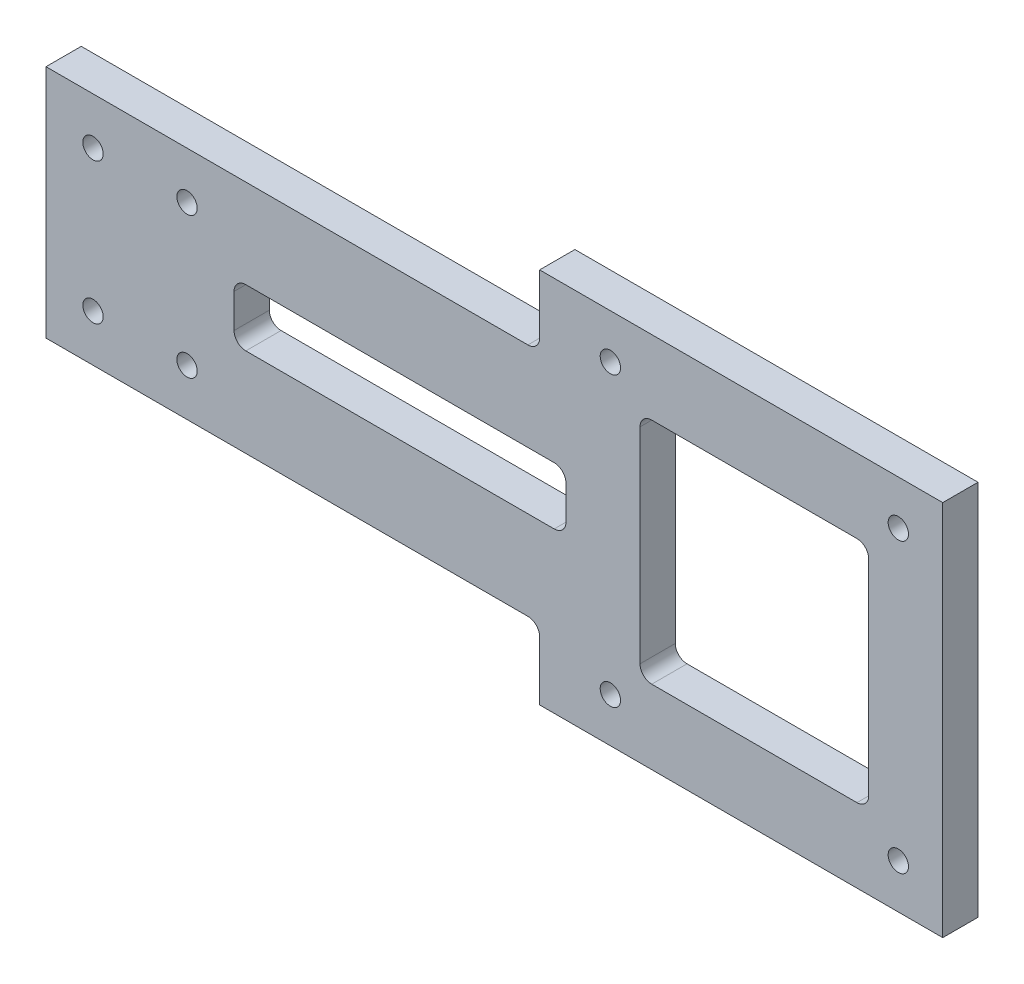
SolidWorks part; units mm, degrees
material "6061-T6 (SS)"
ref_plane "Front" through (0, 0, 0) normal (0, 0, 1) x (1, 0, 0)
ref_plane "Top" through (0, 0, 0) normal (0, 1, 0) x (1, 0, 0)
ref_plane "Right" through (0, 0, 0) normal (1, 0, 0) x (0, 0, -1)
sketch "Sketch1" plane through (0, 0, 0) normal (0, 0, 1) x (1, 0, 0)
  line L0 (101.6, 31.75) -> (101.6, 50.8909)
  line L1 (101.6, 31.75) -> (-31.75, 31.75)
  line L3 (101.6, -31.75) -> (-31.75, -31.75)
  line L4 (-31.75, 31.75) -> (-31.75, -31.75)
  line L5 (-31.75, -31.75) -> (0, 0) construction
  line L6 (0, 0) -> (-31.75, 31.75) construction
  line L7 (101.6, 50.8909) -> (210.4909, 50.8909)
  line L8 (210.4909, 50.8909) -> (210.4909, 30.8909)
  line L9 (210.4909, 30.8909) -> (128.7091, 30.8909)
  line L10 (128.7091, 30.8909) -> (128.7091, -30.8909)
  line L11 (128.7091, -30.8909) -> (210.4909, -30.8909)
  line L12 (210.4909, -30.8909) -> (210.4909, -50.8909)
  line L13 (210.4909, -50.8909) -> (101.6, -50.8909)
  line L14 (101.6, -50.8909) -> (101.6, -31.75)
  line L15 (198.4909, -30.8909) -> (198.4909, -38.8909) construction
  line L16 (198.4909, -38.8909) -> (198.4909, -50.8909) construction
  line L17 (0, 0) -> (159.6, 0) construction
  line L18 (198.4909, -38.8909) -> (120.7091, 38.8909) construction
  line L19 (198.4909, 38.8909) -> (120.7091, -38.8909) construction
  line L20 (128.7091, 30.8909) -> (159.6, 0) construction
  line L21 (159.6, 0) -> (128.7091, -30.8909) construction
  line L22 (198.4909, 38.8909) -> (198.4909, 50.8909) construction
  line L23 (198.4909, 38.8909) -> (210.4909, 38.8909) construction
  line L24 (198.4909, 38.8909) -> (198.4909, 30.8909) construction
  line L25 (120.7091, 38.8909) -> (101.6, 38.8909) construction
  line L26 (0, 0) -> (128.7091, 0) construction
  line L27 (0, 0) -> (101.6, -31.75) construction
  line L28 (0, 0) -> (101.6, 31.75) construction
  line L29 (198.4909, -38.8909) -> (210.4909, -38.8909) construction
  line L30 (159.6, 0) -> (159.6, 30.8909) construction
  line L31 (159.6, 0) -> (128.7091, 0) construction
  circle A0 centre (159.6, 0) radius 55 construction
  point P0 (0, 0)
  point P17 (198.4909, 38.8909)
  point P18 (198.4909, -38.8909)
  point P19 (120.7091, 38.8909)
  point P20 (120.7091, -38.8909)
  dimension "D2" = 110
  dimension "D1" = 63.5
  dimension "D3" = 90
  dimension "D5" = 8
  dimension "D6" = 12
  dimension "D7" = 133.35
  dimension "D9" = 58
  dimension "D10" = 0
extrude "Boss-Extrude1" add sketch "Sketch1" along normal blind 9.525
hole_wizard "M5 Clearance Hole1" positions "Sketch3" profile "Sketch4" hole size "M5" standard "ANSI Metric"
sketch "Sketch3" plane through (0, 0, 9.525) normal (0, 0, 1) x (1, 0, 0)
  line L0 (0, 0) -> (159.6, 0) construction
  line L2 (198.4909, -38.8909) -> (120.7091, 38.8909) construction
  line L4 (198.4909, 38.8909) -> (120.7091, -38.8909) construction
  line L6 (128.7091, 30.8909) -> (159.6, 0) construction
  line L7 (159.6, 0) -> (128.7091, -30.8909) construction
  line L8 (101.6, 31.75) -> (-31.75, 31.75) construction
  line L12 (101.6, -31.75) -> (101.6, -50.8909) construction
  circle A0 centre (159.6, 0) radius 55 construction
  point P0 (198.4909, 38.8909)
  point P2 (198.4909, -38.8909)
  point P4 (120.7091, 38.8909)
  point P6 (120.7091, -38.8909)
  dimension "D1" = 110
  dimension "D2" = 135
  dimension "D3" = 90
  dimension "D4" = 58
sketch "Sketch4" plane through (198.4909, 38.8909, 9.525) normal (1, 0, 0) x (0, -1, 0)
  line L0 (0, 0) -> (0, 20.4024)
  line L1 (0, 20.4024) -> (2.75, 18.75)
  line L2 (2.75, 18.75) -> (2.75, 0)
  line L5 (2.75, 0) -> (0, 0)
  line L10 (0, 20.4024) -> (-2.75, 18.75) construction
  line L11 (0, -6.35) -> (0, 107.95) construction
  dimension "Hole Dia." = 5.5
  dimension "Hole Depth" = 18.75
  dimension "Drill Angle" = 118
fillet "Fillet1" radius 3.175 4 edges at (128.7091, 30.8909, 4.7625) (128.7091, -30.8909, 4.7625) (101.6, -31.75, 4.7625) (101.6, 31.75, 4.7625)
hole_wizard "M5 Clearance Hole2" positions "Sketch5" profile "Sketch6" hole size "M5" standard "ANSI Metric"
sketch "Sketch5" plane through (0, 0, 9.525) normal (0, 0, 1) x (1, 0, 0)
  line L0 (-19.05, 19.05) -> (6.35, 19.05) construction
  line L1 (6.35, 19.05) -> (6.35, -19.05) construction
  line L2 (6.35, -19.05) -> (-19.05, -19.05) construction
  line L3 (-19.05, -19.05) -> (-19.05, 19.05) construction
  line L5 (98.425, 31.75) -> (-31.75, 31.75) construction
  line L9 (-31.75, -31.75) -> (-19.05, -19.05) construction
  line L11 (-19.05, 19.05) -> (-31.75, 31.75) construction
  point P0 (-19.05, 19.05)
  point P2 (6.35, 19.05)
  point P4 (6.35, -19.05)
  point P6 (-19.05, -19.05)
  dimension "D1" = 12.7
  dimension "D2" = 25.4
sketch "Sketch6" plane through (-19.05, 19.05, 9.525) normal (1, 0, 0) x (0, -1, 0)
  line L0 (0, 0) -> (0, 20.4024)
  line L1 (0, 20.4024) -> (2.75, 18.75)
  line L2 (2.75, 18.75) -> (2.75, 0)
  line L5 (2.75, 0) -> (0, 0)
  line L10 (0, 20.4024) -> (-2.75, 18.75) construction
  line L11 (0, -6.35) -> (0, 107.95) construction
  dimension "Hole Dia." = 5.5
  dimension "Hole Depth" = 18.75
  dimension "Drill Angle" = 118
sketch "Sketch7" plane through (0, 0, 9.525) normal (0, 0, 1) x (1, 0, 0)
  line L0 (6.35, 19.05) -> (6.35, 31.75) construction
  line L1 (108.7091, -7.75) -> (19.05, -7.75)
  line L2 (108.7091, -7.75) -> (108.7091, 7.75)
  line L3 (108.7091, 7.75) -> (19.05, 7.75)
  line L4 (19.05, -7.75) -> (19.05, 7.75)
  line L5 (108.7091, -7.75) -> (19.05, 7.75) construction
  line L6 (108.7091, 7.75) -> (19.05, -7.75) construction
  line L7 (128.7091, -27.7159) -> (128.7091, 27.7159) construction
  line L8 (98.425, 31.75) -> (-31.75, 31.75) construction
  line L9 (0, 0) -> (63.8796, 0) construction
  line L10 (6.35, 19.05) -> (19.05, 19.05) construction
  point P0 (63.8796, 0)
  dimension "D1" = 20
  dimension "D2" = 24
extrude "Cut-Extrude1" cut sketch "Sketch7" against normal through all
fillet "Fillet2" radius 3.175 4 edges at (108.7091, -7.75, 4.7625) (108.7091, 7.75, 4.7625) (19.05, 7.75, 4.7625) (19.05, -7.75, 4.7625)
sketch "Sketch8" plane through (0, 0, 9.525) normal (0, 0, 1) x (1, 0, 0)
  line L0 (131.8841, 30.8909) -> (210.4909, 30.8909) construction
  line L1 (210.4909, -30.8909) -> (190.4909, -30.8909)
  line L2 (210.4909, -30.8909) -> (210.4909, 30.8909)
  line L3 (210.4909, 30.8909) -> (190.4909, 30.8909)
  line L4 (190.4909, -30.8909) -> (190.4909, 30.8909)
  line L5 (210.4909, -50.8909) -> (210.4909, -30.8909) construction
extrude "Boss-Extrude2" add sketch "Sketch8" against normal up to surface (9.525 mm away) up to face at (63.8796, 0, 0)
fillet "Fillet3" radius 3.175 2 edges at (190.4909, -30.8909, 4.7625) (190.4909, 30.8909, 4.7625)
